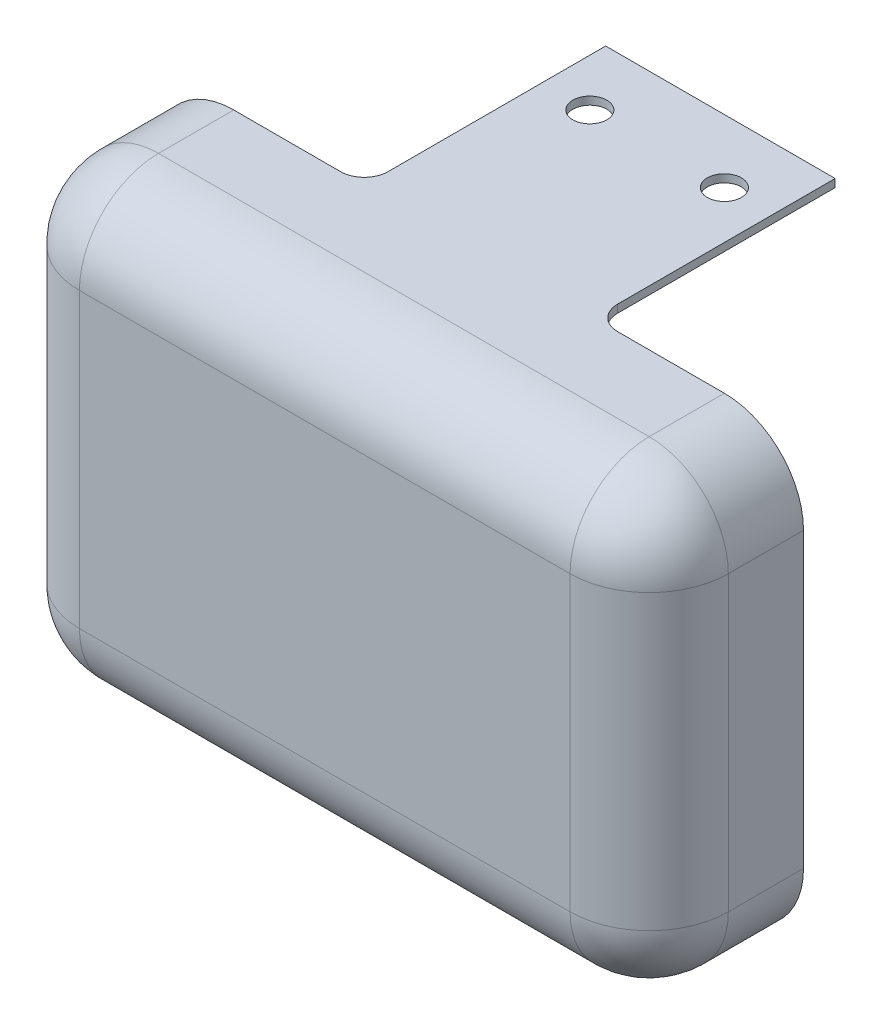
SolidWorks part; units mm, degrees
ref_plane "Front Plane" through (0, 0, 0) normal (0, 0, 1) x (1, 0, 0)
ref_plane "Top Plane" through (0, 0, 0) normal (0, 1, 0) x (1, 0, 0)
ref_plane "Right Plane" through (0, 0, 0) normal (1, 0, 0) x (0, 0, -1)
sketch "Sketch1" plane through (0, 0, 0) normal (0, 0, 1) x (1, 0, 0)
  line L0 (-41, 18.5) -> (-41, -18.5)
  line L1 (-31, -28.5) -> (31, -28.5)
  line L2 (41, -18.5) -> (41, 18.5)
  line L3 (31, 28.5) -> (-31, 28.5)
  line L4 (-40, 18.5) -> (-40, -18.5)
  line L5 (-31, -27.5) -> (31, -27.5)
  line L6 (40, -18.5) -> (40, 18.5)
  line L7 (31, 27.5) -> (-31, 27.5)
  line L8 (-40, 18.5) -> (-40, -18.5)
  line L9 (-31, -27.5) -> (31, -27.5)
  line L10 (40, -18.5) -> (40, 18.5)
  line L11 (31, 27.5) -> (-31, 27.5)
  arc A0 (-41, -18.5) -> (-31, -28.5) centre (-31, -18.5) ccw
  arc A1 (31, -28.5) -> (41, -18.5) centre (31, -18.5) ccw
  arc A2 (41, 18.5) -> (31, 28.5) centre (31, 18.5) ccw
  arc A3 (-31, 28.5) -> (-41, 18.5) centre (-31, 18.5) ccw
  arc A4 (-31, 27.5) -> (-40, 18.5) centre (-31, 18.5) ccw
  arc A5 (-40, -18.5) -> (-31, -27.5) centre (-31, -18.5) ccw
  arc A6 (31, -27.5) -> (40, -18.5) centre (31, -18.5) ccw
  arc A7 (40, 18.5) -> (31, 27.5) centre (31, 18.5) ccw
  arc A8 (-31, 27.5) -> (-40, 18.5) centre (-31, 18.5) ccw
  arc A9 (-40, -18.5) -> (-31, -27.5) centre (-31, -18.5) ccw
  arc A10 (31, -27.5) -> (40, -18.5) centre (31, -18.5) ccw
  arc A11 (40, 18.5) -> (31, 27.5) centre (31, 18.5) ccw
  dimension "D1" = 0
  dimension "D2" = 1
extrude "Boss-Extrude1" add sketch "Sketch1" along normal blind 50 contours L10 A11 L11 A8 L8 A9 L9 A10 | L3 A3 L0 A0 L1 A1 L2 A2 A11 L10 A10 L9 A9 L8 A8 L11 region at (-37.3649, 24.8649, 0) region at (0, 0, 0)
sketch "Sketch2" plane through (-41, 0, 0) normal (-1, 0, 0) x (0, 0, 1)
  line L0 (0, -18.5) -> (0, -28.5) construction
  line L1 (0, -27.5) -> (30.5, -27.5)
  line L2 (0, -27.5) -> (0, 27.5)
  line L3 (0, 27.5) -> (30.5, 27.5)
  line L4 (30.5, -27.5) -> (30.5, 27.5)
  line L5 (-3, -27.5) -> (0, -27.5) construction
  line L6 (-3, 27.5) -> (0, 27.5) construction
  dimension "D1" = 30.5
extrude "Cut-Extrude1" cut sketch "Sketch2" against normal through all
sketch "Sketch3" plane through (0, 28.5, 0) normal (0, 1, 0) x (1, 0, 0)
  line L0 (31, 0) -> (-31, 0) construction
  line L1 (35.3589, -30.5) -> (14.5, -30.5)
  line L2 (35.3589, -30.5) -> (35.3589, 0)
  line L3 (35.3589, 0) -> (14.5, 0)
  line L4 (14.5, -30.5) -> (14.5, 0)
  line L5 (-14.5, -30.5) -> (-14.5, 0) construction
  line L6 (-35.3589, -30.5) -> (-14.5, -30.5)
  line L7 (-35.3589, -30.5) -> (-35.3589, 0)
  line L8 (-35.3589, 0) -> (-14.5, 0)
  line L9 (-14.5, -30.5) -> (-14.5, 0)
  line L10 (14.5, -30.5) -> (14.5, 0) construction
extrude "Cut-Extrude2" cut sketch "Sketch3" against normal through all
sketch "Sketch4" plane through (0, -28.5, 0) normal (0, -1, 0) x (1, 0, 0)
  line L0 (-14.5, 0) -> (14.5, 0) construction
  line L1 (-14.5, 30.5) -> (-8, 30.5)
  line L2 (-14.5, 30.5) -> (-14.5, 0)
  line L3 (-14.5, 0) -> (-8, 0)
  line L4 (-8, 30.5) -> (-8, 0)
  line L5 (14.5, 30.5) -> (8, 30.5)
  line L6 (14.5, 30.5) -> (14.5, 0)
  line L7 (14.5, 0) -> (8, 0)
  line L8 (8, 30.5) -> (8, 0)
  line L9 (-8, 30.5) -> (-8, 0) construction
  line L10 (8, 30.5) -> (8, 0) construction
extrude "Cut-Extrude3" cut sketch "Sketch4" against normal up to surface (1 mm away) up to face at (0, -27.5, 15.25)
fillet "Fillet1" radius 10 8 edges at (38.0711, 25.5711, 50) (41, 0, 50) (38.0711, -25.5711, 50) (0, -28.5, 50) (-38.0711, -25.5711, 50) (-41, 0, 50) (-38.0711, 25.5711, 50) (0, 28.5, 50)
shell "Shell1" thickness 1 removed face at (0, 0, 30.5)
sketch "Sketch5" plane through (0, -28.5, 0) normal (0, -1, 0) x (1, 0, 0)
  circle A0 centre (0, 8) radius 2.15 construction
  circle A1 centre (0, 8) radius 2.15
extrude "Cut-Extrude4" cut sketch "Sketch5" against normal up to surface (1 mm away)
sketch "Sketch6" plane through (0, 28.5, 0) normal (0, 1, 0) x (1, 0, 0)
  circle A0 centre (-8.5, -8) radius 2.15 construction
  circle A1 centre (8.5, -8) radius 2.15 construction
  circle A2 centre (-8.5, -8) radius 2.15
  circle A3 centre (8.5, -8) radius 2.15
extrude "Cut-Extrude5" cut sketch "Sketch6" against normal up to surface (1 mm away)
fillet "Fillet2" radius 3 4 edges at (8, -28, 30.5) (14.5, 28, 30.5) (-14.5, 28, 30.5) (-8, -28, 30.5)
